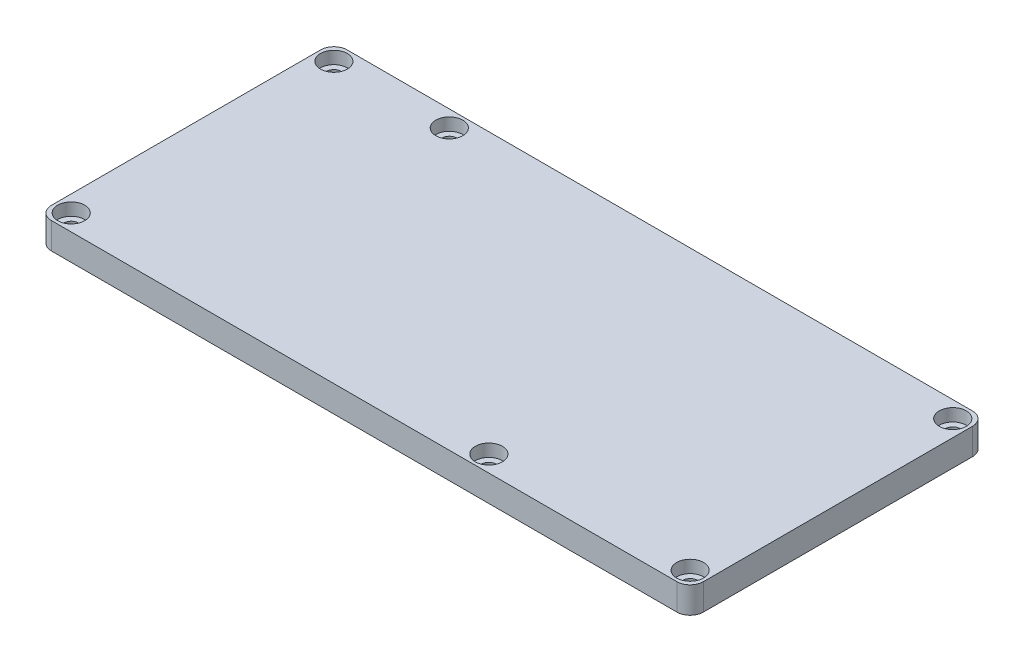
SolidWorks part; units mm, degrees
ref_plane "Front Plane" through (0, 0, 0) normal (0, 0, 1) x (1, 0, 0)
ref_plane "Top Plane" through (0, 0, 0) normal (0, 1, 0) x (1, 0, 0)
ref_plane "Right Plane" through (0, 0, 0) normal (1, 0, 0) x (0, 0, -1)
sketch "Sketch1" plane through (0, 0, 0) normal (0, 1, 0) x (1, 0, 0)
  line L5 (0, 0) -> (156.894, 0)
  line L6 (0, 0) -> (0, 71.1479)
  line L7 (0, 71.1479) -> (156.894, 71.1479)
  line L8 (156.894, 0) -> (156.894, 71.1479)
  dimension "D1" = 156.894
  dimension "D2" = 71.1479
extrude "Boss-Extrude1" add sketch "Sketch1" along normal blind 6.35
fillet "Fillet1" radius 3.175 4 edges at (0, 3.175, -71.1479) (156.894, 3.175, -71.1479) (156.894, 3.175, 0) (0, 3.175, 0)
sketch "Sketch2" plane through (0, 6.35, 0) normal (0, 1, 0) x (1, 0, 0)
  line L0 (3.9688, 67.1792) -> (152.9252, 67.1792) construction
  line L1 (3.9688, 3.9687) -> (152.9252, 3.9687) construction
  line L2 (3.9688, 67.1792) -> (3.9688, 3.9687) construction
  line L3 (153.719, 71.1479) -> (3.175, 71.1479) construction
  line L4 (0, 67.9729) -> (0, 3.175) construction
  circle A0 centre (3.9688, 67.1792) radius 2.54
  circle A1 centre (31.75, 67.1792) radius 2.54
  circle A2 centre (104.4854, 3.9687) radius 2.54
  circle A3 centre (3.9688, 3.9687) radius 2.54
  circle A4 centre (152.9252, 3.9687) radius 2.54
  circle A5 centre (152.9252, 67.1792) radius 2.54
  dimension "D1" = 5.08
  dimension "D2" = 27.7812
  dimension "D3" = 148.9565
  dimension "D4" = 63.2104
  dimension "D5" = 100.5167
  dimension "D6" = 3.9688
  dimension "D7" = 3.9688
hole_wizard "CBORE for M3 SHCS1" positions "Sketch5" profile "Sketch4" counterbore size "M3" standard "ANSI Metric" end condition through all
sketch "Sketch5" plane through (0, 6.35, 0) normal (0, 1, 0) x (1, 0, 0)
  point P0 (3.9688, 67.1792)
  point P3 (31.75, 67.1792)
  point P6 (152.9252, 67.1792)
  point P9 (3.9688, 3.9687)
  point P12 (104.4854, 3.9687)
  point P15 (152.9252, 3.9687)
sketch "Sketch4" plane through (3.9688, 6.35, -67.1792) normal (1, 0, 0) x (0, 0, 1)
  line L0 (0, 0) -> (0, 6.35)
  line L1 (0, 6.35) -> (1.8, 6.35)
  line L3 (1.8, 6.35) -> (1.8, 3)
  line L4 (1.8, 3) -> (3.25, 3)
  line L5 (3.25, 3) -> (3.25, 0)
  line L7 (3.25, 0) -> (0, 0)
  line L11 (0, -6.35) -> (0, 107.95) construction
  dimension "Thru Hole Dia." = 3.6
  dimension "Thru Hole Depth" = 6.35
  dimension "C'Bore Dia." = 6.5
  dimension "C'Bore Depth" = 3
shell "Shell1" thickness 3.175 removed face at (3.9688, 0, -65.3792)
sketch "Sketch8" plane through (0, 3.175, 0) normal (0, -1, 0) x (1, 0, 0)
  line L0 (8.89, -5.08) -> (22.86, -5.08) construction
  line L1 (8.89, -5.08) -> (8.89, -18.288) construction
  line L2 (8.89, -18.288) -> (22.86, -18.288) construction
  line L3 (22.86, -5.08) -> (22.86, -18.288) construction
  line L4 (8.89, -28.462) -> (22.86, -28.462) construction
  line L5 (8.89, -28.462) -> (8.89, -41.67) construction
  line L6 (8.89, -41.67) -> (22.86, -41.67) construction
  line L7 (22.86, -28.462) -> (22.86, -41.67) construction
  line L8 (8.89, -51.8439) -> (22.86, -51.8439) construction
  line L9 (8.89, -51.8439) -> (8.89, -65.0519) construction
  line L10 (8.89, -65.0519) -> (22.86, -65.0519) construction
  line L11 (22.86, -51.8439) -> (22.86, -65.0519) construction
  line L12 (122.911, -28.9839) -> (136.881, -28.9839) construction
  line L13 (122.911, -28.9839) -> (122.911, -42.1919) construction
  line L14 (122.911, -42.1919) -> (136.881, -42.1919) construction
  line L15 (136.881, -28.9839) -> (136.881, -42.1919) construction
  line L16 (153.719, -71.1479) -> (3.175, -71.1479) construction
  line L17 (0, -67.9729) -> (0, -3.175) construction
  line L18 (12.065, -8.255) -> (19.685, -8.255)
  line L19 (19.685, -8.255) -> (19.685, -15.113)
  line L20 (12.065, -15.113) -> (19.685, -15.113)
  line L21 (12.065, -8.255) -> (12.065, -15.113)
  line L22 (12.065, -31.637) -> (19.685, -31.637)
  line L23 (19.685, -31.637) -> (19.685, -38.495)
  line L24 (12.065, -38.495) -> (19.685, -38.495)
  line L25 (12.065, -31.637) -> (12.065, -38.495)
  line L26 (12.065, -55.0189) -> (19.685, -55.0189)
  line L27 (19.685, -55.0189) -> (19.685, -61.8769)
  line L28 (12.065, -61.8769) -> (19.685, -61.8769)
  line L29 (12.065, -55.0189) -> (12.065, -61.8769)
  line L30 (126.086, -32.1589) -> (133.706, -32.1589)
  line L31 (133.706, -32.1589) -> (133.706, -39.0169)
  line L32 (126.086, -39.0169) -> (133.706, -39.0169)
  line L33 (126.086, -32.1589) -> (126.086, -39.0169)
  dimension "D1" = 13.208
  dimension "D2" = 13.97
  dimension "D3" = 23.382
  dimension "D4" = 46.7639
  dimension "D5" = 100.051
  dimension "D6" = 22.86
  dimension "D7" = 6.096
  dimension "D8" = 8.89
  dimension "D9" = 3.175
extrude "Boss-Extrude2" add sketch "Sketch8" along normal blind 6.35
sketch "Sketch9" plane through (0, 3.175, 0) normal (0, -1, 0) x (1, 0, 0)
  line L0 (12.065, -15.113) -> (12.065, -31.637) construction
  line L1 (12.065, -38.495) -> (12.065, -55.0189) construction
  line L2 (19.685, -55.0189) -> (12.065, -55.0189) construction
  line L3 (31.75, -67.1792) -> (31.75, -5.842) construction
  line L4 (104.4854, -3.9687) -> (104.4854, -65.3059) construction
  line L5 (133.706, -39.0169) -> (133.706, -32.1589) construction
  line L6 (3.175, 0) -> (153.719, 0) construction
  line L7 (0, -67.9729) -> (0, -3.175) construction
  line L8 (153.719, -71.1479) -> (3.175, -71.1479) construction
  line L9 (156.894, -3.175) -> (156.894, -67.9729) construction
  circle A0 centre (5.842, -23.375) radius 4.318 construction
  circle A1 centre (5.842, -46.757) radius 4.318 construction
  circle A2 centre (104.4854, -65.3059) radius 4.318 construction
  circle A3 centre (31.75, -5.842) radius 4.318 construction
  circle A4 centre (151.052, -35.5879) radius 4.318 construction
  circle A5 centre (5.842, -23.375) radius 5.842
  circle A6 centre (5.842, -46.757) radius 5.842
  circle A7 centre (31.75, -5.842) radius 5.842
  circle A8 centre (104.4854, -65.3059) radius 5.842
  circle A9 centre (151.052, -35.5879) radius 5.842
  point P14 (12.065, -23.375)
  point P20 (12.065, -46.757)
  point P27 (133.706, -35.5879)
  dimension "D1" = 8.636
  dimension "D2" = 1.524
extrude "Boss-Extrude3" add sketch "Sketch9" along normal up to surface (3.175 mm away) up to face at (75.0039, 0, -35.574)
sketch "Sketch10" plane through (0, 6.35, 0) normal (0, 1, 0) x (1, 0, 0)
  circle A0 centre (31.75, 5.842) radius 4.318 construction
  circle A1 centre (5.842, 23.375) radius 4.318 construction
  circle A2 centre (5.842, 46.757) radius 4.318 construction
  circle A3 centre (104.4854, 65.3059) radius 4.318 construction
  circle A4 centre (151.052, 35.5879) radius 4.318 construction
  circle A5 centre (31.75, 5.842) radius 4.318
  circle A6 centre (5.842, 23.375) radius 4.318
  circle A7 centre (5.842, 46.757) radius 4.318
  circle A8 centre (104.4854, 65.3059) radius 4.318
  circle A9 centre (151.052, 35.5879) radius 4.318
extrude "Cut-Extrude2" cut sketch "Sketch10" against normal blind 2.794 from offset 1.5875 offset against normal yes
equation "\"D7@Sketch2\"=\"D6@Sketch2\""
